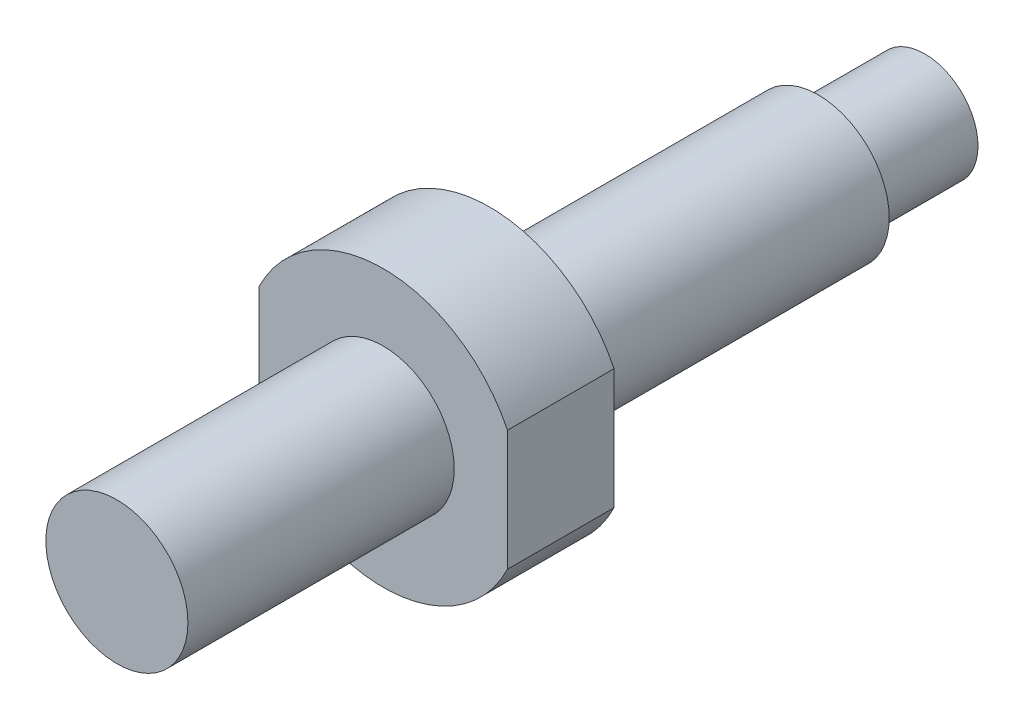
SolidWorks part; units mm, degrees
material "普通碳钢"
ref_plane "前视基准面" through (0, 0, 0) normal (0, 0, 1) x (1, 0, 0)
ref_plane "上视基准面" through (0, 0, 0) normal (0, 1, 0) x (1, 0, 0)
ref_plane "右视基准面" through (0, 0, 0) normal (1, 0, 0) x (0, 0, -1)
sketch "草图2" plane through (0, 0, 0) normal (1, 0, 0) x (0, 0, -1)
  line L0 (0, 0) -> (128.8801, 0) construction
  line L1 (0, 0) -> (0, 4)
  line L2 (0, 4) -> (15, 4)
  line L7 (15, 4) -> (15, 9)
  line L8 (15, 9) -> (21, 9)
  line L9 (21, 9) -> (21, 4)
  line L10 (21, 4) -> (39.5, 4)
  line L11 (39.5, 4) -> (39.5, 0)
  line L12 (0, 0) -> (39.5, 0)
  dimension "D1" = 15
  dimension "D2" = 4
  dimension "D6" = 6
  dimension "D7" = 4
  dimension "D8" = 9
  dimension "D9" = 18.5
revolve "旋转1" add sketch "草图2" angle 360 about L0
cosmetic thread "装饰螺纹线1" parameters "D1"=11, "D2"=7
sketch "草图3" plane through (0, 0, -15) normal (0, 0, 1) x (1, 0, 0)
  line L0 (0, 0) -> (0, -7.8258) construction
  line L1 (-7, 8.3859) -> (-15, 8.3859)
  line L2 (7, -8.438) -> (15, -8.438)
  line L3 (7, -8.438) -> (7, 8.3859)
  line L4 (7, 8.3859) -> (15, 8.3859)
  line L5 (15, -8.438) -> (15, 8.3859)
  line L6 (-7, -8.438) -> (-15, -8.438)
  line L7 (-7, -8.438) -> (-7, 8.3859)
  line L8 (-15, -8.438) -> (-15, 8.3859)
  dimension "D1" = 7
  dimension "D2" = 8
extrude "切除-拉伸1" cut sketch "草图3" against normal blind 10
sketch "草图5" plane through (0, 0, -21) normal (0, 0, -1) x (-1, 0, 0)
  circle A0 centre (0, 0) radius 7.7778
extrude "切除-拉伸2" cut sketch "草图5" against normal blind 10 flip side to cut
ref_axis "基准轴1" through (0, 0, -39.5) along (0, 0, 1)
sketch "草图6" plane through (0, 0, -39.5) normal (0, 0, -1) x (-1, 0, 0)
  circle A0 centre (0, 0) radius 3
  dimension "D1" = 6
extrude "凸台-拉伸1" add sketch "草图6" along normal blind 6
cosmetic thread "装饰螺纹线2" parameters "D1"=6, "D2"=5
